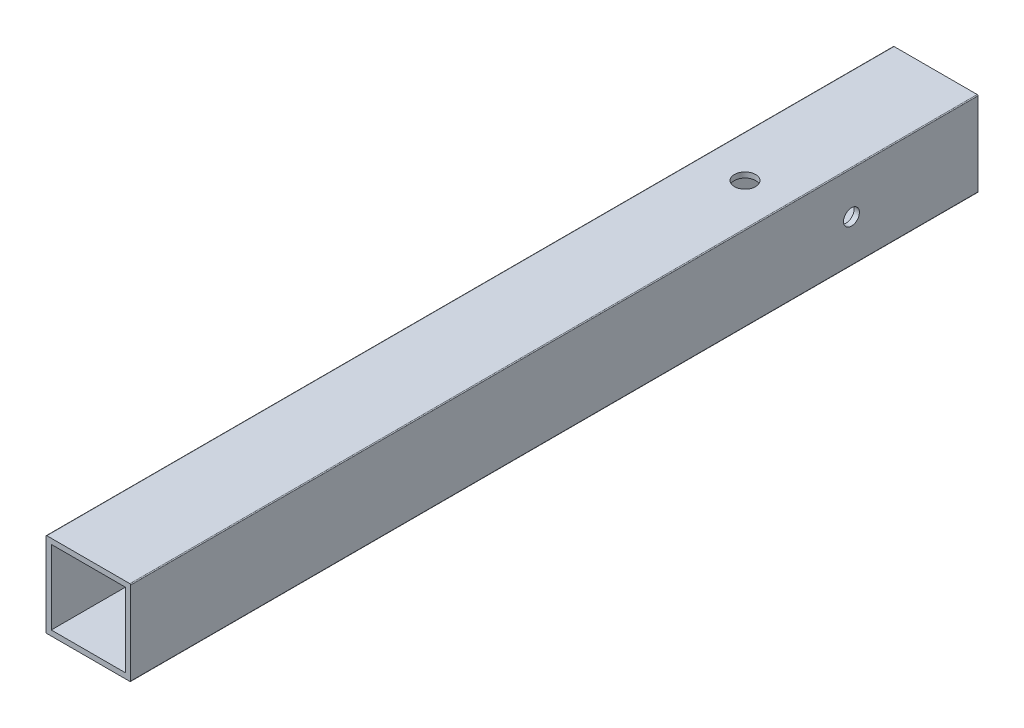
SolidWorks part; units mm, degrees
material "1060 Alloy"
ref_plane "Front Plane" through (0, 0, 0) normal (0, 0, 1) x (1, 0, 0)
ref_plane "Top Plane" through (0, 0, 0) normal (0, 1, 0) x (1, 0, 0)
ref_plane "Right Plane" through (0, 0, 0) normal (1, 0, 0) x (0, 0, -1)
ref_plane "Plane1" through (0, 0, 0) normal (0, 0, -1) x (-1, 0, 0)
sketch "Sketch1" plane through (0, 0, 0) normal (0, 0, -1) x (-1, 0, 0)
  line L4 (1.5875, -1.3335) -> (1.5875, 23.5585)
  line L5 (1.3335, 23.8125) -> (-23.5585, 23.8125)
  line L6 (-23.8125, 23.5585) -> (-23.8125, -1.3335)
  line L7 (-23.5585, -1.5875) -> (1.3335, -1.5875)
  line L9 (0, 22.225) -> (-22.225, 22.225)
  line L10 (0, 22.225) -> (0, 0)
  line L11 (0, 0) -> (-22.225, 0)
  line L12 (-22.225, 22.225) -> (-22.225, 0)
  line L13 (0, 22.225) -> (-22.225, 0) construction
  line L14 (0, 0) -> (-22.225, 22.225) construction
  arc A4 (1.3335, -1.5875) -> (1.5875, -1.3335) centre (1.3335, -1.3335) ccw
  arc A5 (1.5875, 23.5585) -> (1.3335, 23.8125) centre (1.3335, 23.5585) ccw
  arc A6 (-23.5585, 23.8125) -> (-23.8125, 23.5585) centre (-23.5585, 23.5585) ccw
  arc A7 (-23.8125, -1.3335) -> (-23.5585, -1.5875) centre (-23.5585, -1.3335) ccw
  point P24 (-11.1125, 11.1125)
  dimension "D1" = 25.4
  dimension "D2" = 25.4
  dimension "D3" = 1.5875
  dimension "D4" = 1.5875
  dimension "D5" = 1.5875
extrude "Boss-Extrude1" add sketch "Sketch1" against normal blind 254
sketch "Sketch2" plane through (-1.5875, 0, 0) normal (-1, 0, 0) x (0, 0, 1)
  line L0 (0, -1.3335) -> (0, 23.5585) construction
  line L1 (254, -1.3335) -> (0, -1.3335) construction
  line L2 (254, -1.3335) -> (254, 23.5585) construction
  circle A0 centre (12.6975, 11.3665) radius 1.5875
  circle A1 centre (241.3, 11.3665) radius 1.5875
  circle A2 centre (76.2, 11.3665) radius 6.35
  circle A3 centre (177.8, 11.3665) radius 6.35
  point P4 (0, 11.1125)
  dimension "D1" = 3.175
  dimension "D2" = 12.7
  dimension "D3" = 12.7
  dimension "D4" = 3.175
  dimension "D5" = 12.7
  dimension "D6" = 12.7
  dimension "D7" = 12.7
  dimension "D8" = 12.7
  dimension "D9" = 76.2
  dimension "D10" = 12.7
  dimension "D11" = 12.7
  dimension "D12" = 76.2
extrude "Cut-Extrude1" [suppressed] cut sketch "Sketch2" against normal through all
sketch "Sketch4" plane through (23.8125, 0, 0) normal (1, 0, 0) x (0, 0, -1)
  line L7 (-40.3145, 11.1125) -> (-35.552, 11.1125)
  line L8 (0, 23.5585) -> (0, -1.3335) construction
  line L9 (0, 11.1125) -> (-49.6378, 11.1125)
  circle A2 centre (-37.9333, 11.1125) radius 2.3812
  dimension "D1" = 4.7625
extrude "Cut-Extrude2" cut sketch "Sketch4" against normal through all contours A2
sketch "Sketch5" plane through (0, 23.8125, 0) normal (0, 1, 0) x (1, 0, 0)
  line L0 (11.1125, 0) -> (11.1125, -57.15) construction
  line L1 (-1.3335, 0) -> (23.5585, 0) construction
  circle A0 centre (11.1125, -57.15) radius 3.175
  dimension "D1" = 6.35
  dimension "D2" = 57.15
extrude "Cut-Extrude3" cut sketch "Sketch5" against normal blind 50.8
